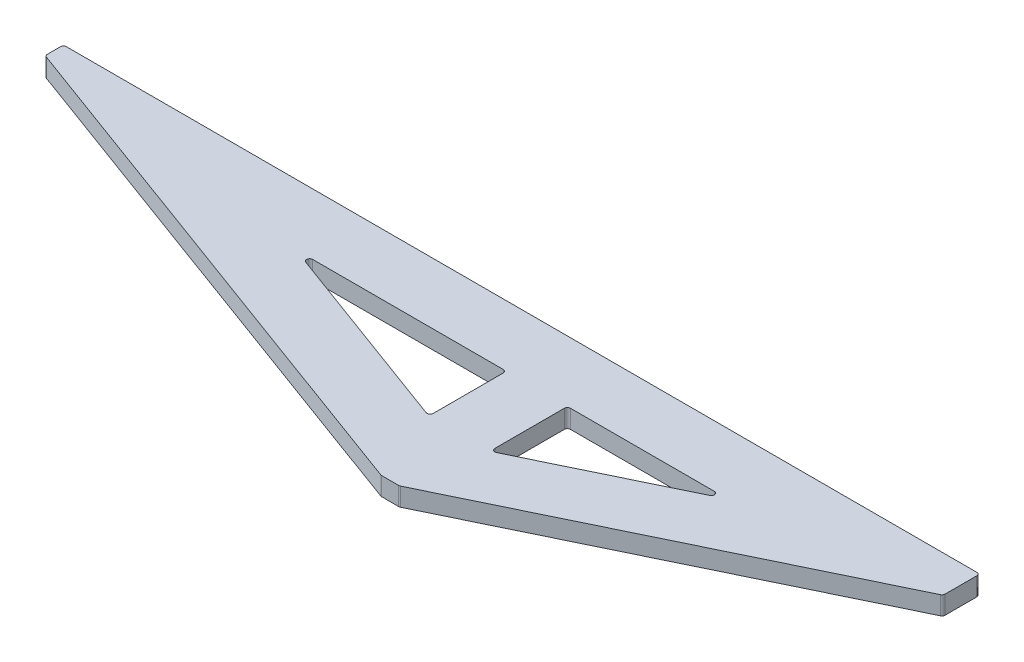
SolidWorks part; units mm, degrees
material "Beech"
ref_plane "Спереди" through (0, 0, 0) normal (0, 0, 1) x (1, 0, 0)
ref_plane "Сверху" through (0, 0, 0) normal (0, 1, 0) x (1, 0, 0)
ref_plane "Справа" through (0, 0, 0) normal (1, 0, 0) x (0, 0, -1)
sketch "Sketch1" plane through (0, 0, 0) normal (0, 1, 0) x (1, 0, 0)
  line L0 (0, 0) -> (300, 0)
  line L1 (300, 0) -> (300, -12)
  line L2 (300, -12) -> (180, -70)
  line L3 (180, -70) -> (174, -70)
  line L4 (174, -70) -> (0, -6)
  line L5 (0, -6) -> (0, 0)
  dimension "D1" = 300
  dimension "D2" = 6
  dimension "D3" = 12
  dimension "D4" = 6
  dimension "D5" = 120
  dimension "D6" = 58
extrude "support" add sketch "Sketch1" along normal blind 6
sketch "Sketch2" plane through (0, 6, 0) normal (0, 1, 0) x (1, 0, 0)
  line L0 (95.999, -20) -> (164.9883, -20)
  line L1 (164.9883, -20) -> (164.9883, -45.3754)
  line L2 (95.999, -20) -> (164.9883, -45.3754)
  line L3 (184.9883, -20) -> (184.9883, -45.3754)
  line L4 (184.9883, -45.3754) -> (237.4891, -20)
  line L5 (237.4891, -20) -> (184.9883, -20)
  line L6 (300, 0) -> (0, 0) construction
  line L8 (0, -6) -> (174, -70) construction
  line L9 (180, -70) -> (300, -12) construction
  dimension "D1" = 20
  dimension "D2" = 20
  dimension "D3" = 20
  dimension "D4" = 20
extrude "lite" cut sketch "Sketch2" against normal through all
fillet "fillet" radius 1 12 edges at (300, 3, 0) (300, 3, 12) (180, 3, 70) (174, 3, 70) (0, 3, 0) (0, 3, 6) (237.4891, 3, 20) (184.9883, 3, 45.3754) (184.9883, 3, 20) (164.9883, 3, 20) (164.9883, 3, 45.3754) (95.999, 3, 20)
